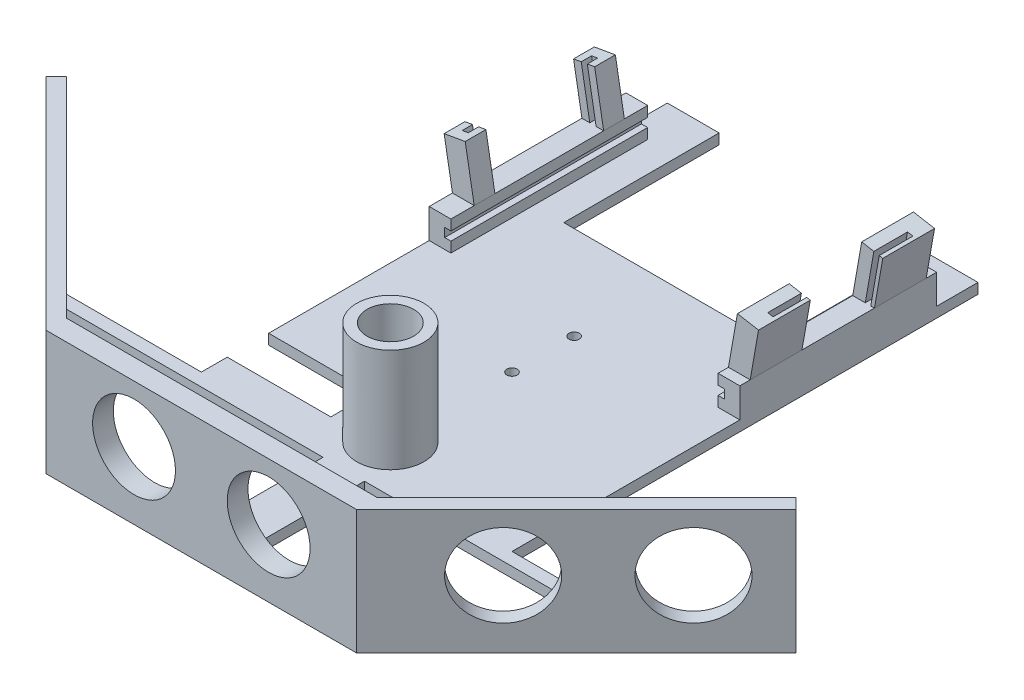
SolidWorks part; units mm, degrees
ref_plane "Front Plane" through (0, 0, 0) normal (0, 0, 1) x (1, 0, 0)
ref_plane "Top Plane" through (0, 0, 0) normal (0, 1, 0) x (1, 0, 0)
ref_plane "Right Plane" through (0, 0, 0) normal (1, 0, 0) x (0, 0, -1)
sketch "Sketch1" plane through (0, 0, 0) normal (0, 0, 1) x (1, 0, 0)
  line L0 (55, 0) -> (-55, 0) construction
  line L1 (30, -11) -> (-30, -11)
  line L2 (30, -11) -> (30, 11)
  line L3 (30, 11) -> (-30, 11)
  line L4 (-30, -11) -> (-30, 11)
  line L5 (30, -11) -> (-30, 11) construction
  line L6 (30, 11) -> (-30, -11) construction
  circle A0 centre (-13, 0) radius 8
  circle A1 centre (13, 0) radius 8
  point P0 (0, 0)
  dimension "D3" = 16
  dimension "D4" = 16
  dimension "D1" = 26
  dimension "D2" = 13
  dimension "D5" = 60
  dimension "D6" = 22
extrude "Boss-Extrude1" add sketch "Sketch1" along normal blind 4
ref_plane "Plane1" through (0, -11, 0) normal (0, -1, 0) x (-1, 0, 0)
sketch "Sketch2" plane through (0, -11, 0) normal (0, -1, 0) x (-1, 0, 0)
  line L0 (0, 2.2) -> (0, -2.2) construction
  line L1 (-30, 116) -> (-20, 116)
  line L3 (-30, -4) -> (30, -4)
  line L4 (30, 116) -> (30, 39)
  line L5 (-30, 116) -> (30, -4) construction
  line L6 (-30, -4) -> (-16.25, 23.5) construction
  line L7 (30, -4) -> (-30, -4) construction
  line L14 (-30, 26) -> (-60, 26)
  line L15 (-30, -4) -> (-60, 26)
  line L16 (30, 26) -> (60, 26)
  line L17 (60, 26) -> (30.0024, -4)
  line L18 (30.0024, -4) -> (30, -4)
  line L19 (-53.5, 23.5) -> (-30, 0)
  line L20 (-53.5, 23.5) -> (-4, 23.5)
  line L21 (-30, 0) -> (-4, 0)
  line L22 (53.4981, 23.5) -> (30, 0)
  line L23 (30, 0) -> (-30, 0) construction
  line L24 (4, 0) -> (4, 23.5)
  line L27 (-4, 0) -> (-4, 23.5)
  line L28 (4, 23.5) -> (53.4981, 23.5)
  line L29 (4, 0) -> (30, 0)
  line L36 (30, 39) -> (10, 39)
  line L37 (30, 31) -> (10, 31)
  line L38 (10, 39) -> (10, 31)
  line L39 (30, 31) -> (30, 26)
  line L40 (0, 56) -> (30, 116) construction
  line L41 (-30, 116) -> (-30, 26)
  line L43 (-20, 116) -> (-20, 86)
  line L44 (20, 116) -> (20, 86)
  line L45 (-20, 86) -> (20, 86)
  line L46 (20, 116) -> (30, 116)
  line L47 (-30, -4) -> (-30, 0) construction
  line L48 (30, -4) -> (30, 0) construction
  point P0 (0, 56)
  dimension "D2" = 120
  dimension "D3" = 30
  dimension "D4" = 135
  dimension "D6" = 30
  dimension "D9" = 2.83
  dimension "D10" = 0
  dimension "D11" = 2.5
  dimension "D12" = 4
  dimension "D13" = 4
  dimension "D14" = 10
  dimension "D15" = 20
  dimension "D16" = 10
  dimension "D17" = 30
  dimension "D18" = 8
  dimension "D19" = 5
  dimension "D20" = 60
extrude "Boss-Extrude2" add sketch "Sketch2" along normal blind 2
sketch "Sketch4" plane through (0, 0, 0) normal (0, 0, 1) x (1, 0, 0)
  line L0 (-25.8, -11) -> (-25.8, -9)
  line L1 (-55, -11) -> (55, -11) construction
  line L2 (-25.8, -9) -> (-27, -9)
  line L3 (-27, -9) -> (-27, -7.3)
  line L4 (-27, -7.3) -> (-25.8, -7.3)
  line L5 (-25.8, -7.3) -> (-25.8, -5.3)
  line L6 (-25.8, -5.3) -> (-30, -5.3)
  line L7 (-30, -5.3) -> (-30, -11)
  line L8 (-30, -11) -> (-25.8, -11)
  line L9 (0, -21.4873) -> (0, 18.1435) construction
  line L10 (0, -2.2) -> (0, 2.2) construction
  line L11 (30, -5.3) -> (30, -11)
  line L12 (30, -11) -> (25.8, -11)
  line L13 (25.8, -11) -> (25.8, -9)
  line L14 (25.8, -9) -> (27, -9)
  line L15 (27, -9) -> (27, -7.3)
  line L16 (27, -7.3) -> (25.8, -7.3)
  line L17 (25.8, -7.3) -> (25.8, -5.3)
  line L18 (25.8, -5.3) -> (30, -5.3)
  line L19 (-30, -13) -> (-30, -11) construction
  dimension "D1" = 1.7
  dimension "D2" = 2
  dimension "D3" = 2
  dimension "D4" = 27
  dimension "D5" = 1.2
extrude "Boss-Extrude3" add sketch "Sketch4" against normal blind 38 from offset 70 offset against normal yes
sketch "Sketch5" plane through (0, -13, 0) normal (0, -1, 0) x (1, 0, 0)
  line L0 (1.2092, 14) -> (66.2092, -106) construction
  line L1 (66.2092, 14) -> (1.2092, -106) construction
  line L2 (0, -2.2) -> (0, 2.2) construction
  line L4 (-30.0024, 4) -> (-60, -26) construction
  line L6 (-60, -26) -> (-30, -26) construction
  circle A0 centre (18.7092, -56) radius 1.2
  circle A1 centre (15, -56) radius 1.2
  circle A2 centre (15, -68) radius 1.2
  circle A3 centre (18.7092, -68) radius 1.2
  point P10 (33.7092, -46)
  dimension "D1" = 2.4
  dimension "D4" = 2.4
  dimension "D7" = 2.4
  dimension "D8" = 2.4
  dimension "D2" = 12
  dimension "D3" = 15
  dimension "D5" = 10
  dimension "D6" = 15
  dimension "D9" = 65
  dimension "D10" = 120
  dimension "D11" = 15
  dimension "D12" = 40
ref_plane "Plane2" through (0.1284, -0.7281, 0) normal (-0.1736, 0.9848, 0) x (0, 0, 1)
sketch "Sketch7" plane through (0.1284, -0.7281, 0) normal (-0.1736, 0.9848, 0) x (0, 0, 1)
  line L0 (-74.5, -26.3284) -> (-74.5, -30.4646)
  line L1 (-108, -26.3284) -> (-70, -26.3284) construction
  line L2 (-108, -30.4646) -> (-70, -30.4646) construction
  line L3 (-74.5, -30.4646) -> (-78.5, -30.4646)
  line L4 (-78.5, -30.4646) -> (-78.5, -28.9646)
  line L5 (-78.5, -28.9646) -> (-76.5, -28.9646)
  line L6 (-76.5, -28.9646) -> (-76.5, -27.7646)
  line L7 (-76.5, -27.7646) -> (-78.5, -27.7646)
  line L8 (-78.5, -27.7646) -> (-78.5, -26.3284)
  line L9 (-78.5, -26.3284) -> (-74.5, -26.3284)
  line L10 (-89, -30.4646) -> (-89, 11.3249) construction
  line L11 (-101.5, -27.7646) -> (-99.5, -27.7646)
  line L12 (-101.5, -28.9646) -> (-101.5, -27.7646)
  line L13 (-99.5, -28.9646) -> (-101.5, -28.9646)
  line L14 (-99.5, -30.4646) -> (-99.5, -28.9646)
  line L15 (-103.5, -30.4646) -> (-99.5, -30.4646)
  line L16 (-103.5, -26.3284) -> (-103.5, -30.4646)
  line L17 (-99.5, -26.3284) -> (-103.5, -26.3284)
  line L18 (-99.5, -27.7646) -> (-99.5, -26.3284)
  dimension "D1" = 1.2
  dimension "D2" = 2
  dimension "D3" = 2
  dimension "D4" = 12.5
  dimension "D5" = 1.5
extrude "Boss-Extrude5" add sketch "Sketch7" along normal blind 10
ref_plane "Plane3" through (-0.1284, -0.7281, 0) normal (0.1736, 0.9848, 0) x (0, 0, 1)
sketch "Sketch8" plane through (-0.1284, -0.7281, 0) normal (0.1736, 0.9848, 0) x (0, 0, 1)
  line L0 (-82, 26.3284) -> (-82, 28.7146)
  line L1 (-108, 26.3284) -> (-70, 26.3284) construction
  line L2 (-82, 28.7146) -> (-75.5, 28.7146)
  line L3 (-75.5, 28.7146) -> (-75.5, 29.7646)
  line L4 (-75.5, 29.7646) -> (-82, 29.7646)
  line L5 (-82, 29.7646) -> (-82, 30.4646)
  line L6 (-108, 30.4646) -> (-70, 30.4646) construction
  line L7 (-82, 30.4646) -> (-72, 30.4646)
  line L8 (-72, 30.4646) -> (-72, 26.3284)
  line L9 (-72, 26.3284) -> (-82, 26.3284)
  line L10 (-89, 26.3284) -> (-89, 55.5373) construction
  line L11 (-96, 29.7646) -> (-96, 30.4646)
  line L12 (-96, 28.7146) -> (-102.5, 28.7146)
  line L13 (-102.5, 28.7146) -> (-102.5, 29.7646)
  line L14 (-102.5, 29.7646) -> (-96, 29.7646)
  line L15 (-96, 30.4646) -> (-106, 30.4646)
  line L16 (-106, 30.4646) -> (-106, 26.3284)
  line L17 (-106, 26.3284) -> (-96, 26.3284)
  line L18 (-96, 26.3284) -> (-96, 28.7146)
  dimension "D1" = 1.05
  dimension "D2" = 0.7
  dimension "D3" = 7
  dimension "D4" = 10
  dimension "D5" = 6.5
extrude "Boss-Extrude6" add sketch "Sketch8" along normal blind 10
sketch "Sketch10" plane through (0, -13, 0) normal (0, -1, 0) x (1, 0, 0)
  line L0 (0, -2.2) -> (0, 2.2) construction
  circle A0 centre (0, -56) radius 1
  circle A2 centre (0, -68) radius 1
  dimension "D1" = 2
  dimension "D2" = 2
extrude "Cut-Extrude1" cut sketch "Sketch10" against normal blind 4
ref_plane "Plane4" through (17, 0, 17) normal (0.7071, 0, 0.7071) x (0, 1, 0)
sketch "Sketch12" plane through (17, 0, 17) normal (0.7071, 0, 0.7071) x (0, 1, 0)
  line L0 (11, -18.3848) -> (-13, -18.3848)
  line L1 (11, -18.3848) -> (11, -78.3848)
  line L2 (-13, -18.3848) -> (-13, -78.3848)
  line L3 (11, -78.3848) -> (-13, -78.3848)
  line L4 (-13, -60.8112) -> (-13, -18.3848) construction
  circle A0 centre (0, -38.3848) radius 8
  circle A1 centre (0, -64.3848) radius 8
  dimension "D1" = 16
  dimension "D5" = 16
  dimension "D2" = 20
  dimension "D3" = 60
  dimension "D4" = 11
  dimension "D6" = 26
extrude "Boss-Extrude7" add sketch "Sketch12" against normal blind 2.83
ref_axis "Axis1" through (60, -11, -26) along (0, -1, 0)
mirror "Mirror2" about plane through (0, 0, 0) normal (1, 0, 0) of "Boss-Extrude7"
sketch "Sketch13" plane through (0, -11, 0) normal (0, 1, 0) x (1, 0, 0)
  line L0 (4, 23.5) -> (53.4978, 23.5) construction
  circle A0 centre (0, 32.5) radius 4.5
  circle A1 centre (0, 32.5) radius 6.5
  dimension "D1" = 2
  dimension "D2" = 9
  dimension "D3" = 9
extrude "Boss-Extrude8" add sketch "Sketch13" along normal blind 20
